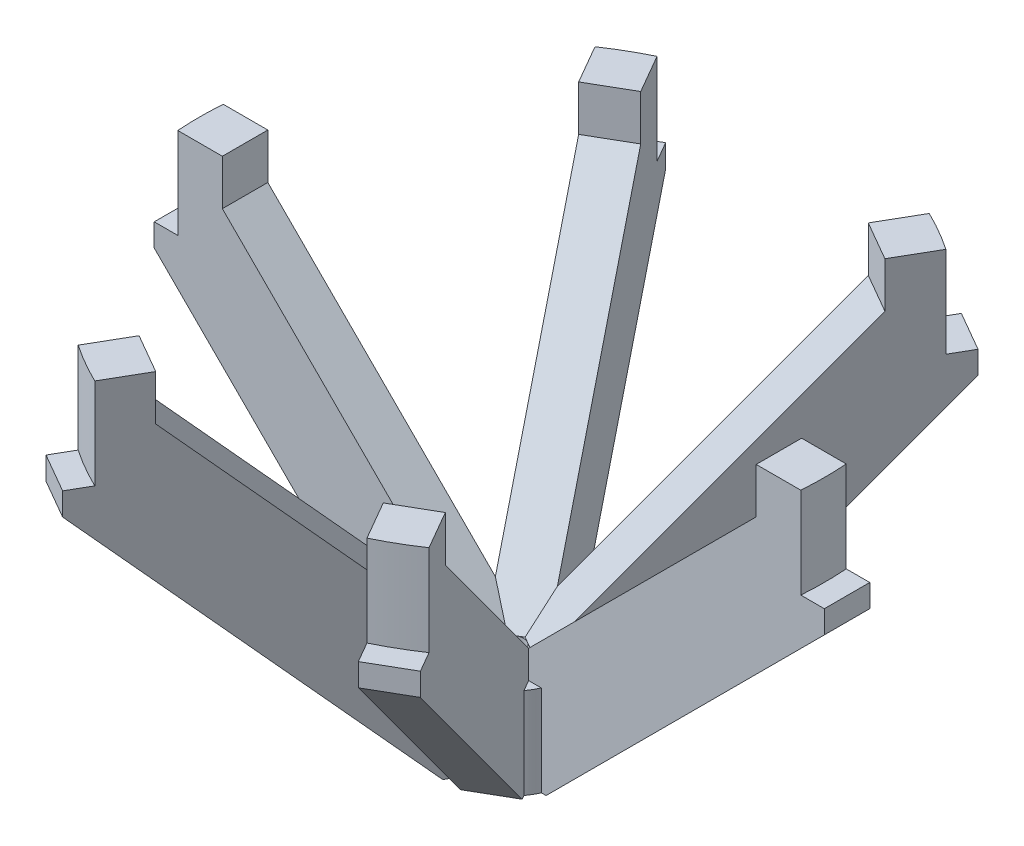
SolidWorks part; units mm, degrees
ref_plane "Front Plane" through (0, 0, 0) normal (0, 0, 1) x (1, 0, 0)
ref_plane "Top Plane" through (0, 0, 0) normal (0, 1, 0) x (1, 0, 0)
ref_plane "Right Plane" through (0, 0, 0) normal (1, 0, 0) x (0, 0, -1)
sketch "Sketch1" plane through (0, 0, 0) normal (0, 1, 0) x (1, 0, 0)
  circle A0 centre (0, 0) radius 0.8
  circle A1 centre (0, 0) radius 4
  dimension "D1" = 1.6
  dimension "D2" = 3.2
extrude "Boss-Extrude1" add sketch "Sketch1" along normal blind 6.4
sketch "Sketch2" plane through (0, 0, 0) normal (0, 0, 1) x (1, 0, 0)
  line L0 (-4, 0) -> (-23.6, 19.6)
  line L1 (-0.8, 6.4) -> (-0.8, 0)
  line L2 (-0.8, 0) -> (-4, 0)
  line L3 (-0.8, 6.4) -> (-18.8, 24.4)
  line L5 (-22, 21.2) -> (-22, 27.6)
  line L6 (-22, 27.6) -> (-18.8, 27.6)
  line L7 (-18.8, 27.6) -> (-18.8, 24.4)
  line L8 (-22, 21.2) -> (-23.6, 21.2)
  line L9 (-23.6, 21.2) -> (-23.6, 19.6)
  dimension "D1" = 22
  dimension "D2" = 3.2
  dimension "D3" = 6.4
  dimension "D4" = 1.6
  dimension "D5" = 45
  dimension "D6" = 1.6
extrude "Boss-Extrude2" add sketch "Sketch2" along normal blind 1.6 and the other way blind 1.6
pattern_circular "CirPattern1" count 6 over 360 about axis through (0, 6.4, 0) along (0, -1, 0) of "Boss-Extrude2" reverse direction yes
sketch "Sketch3" plane through (0, 27.6, 0) normal (0, 1, 0) x (1, 0, 0)
  line L0 (-22, 1.6) -> (-22, -1.6) construction
  circle A0 centre (0, 0) radius 22
  circle A1 centre (0, 0) radius 23.6542
extrude "Cut-Extrude1" cut sketch "Sketch3" against normal up to surface (6.4 mm away) up to face at (-22.8, 21.2, 0)
